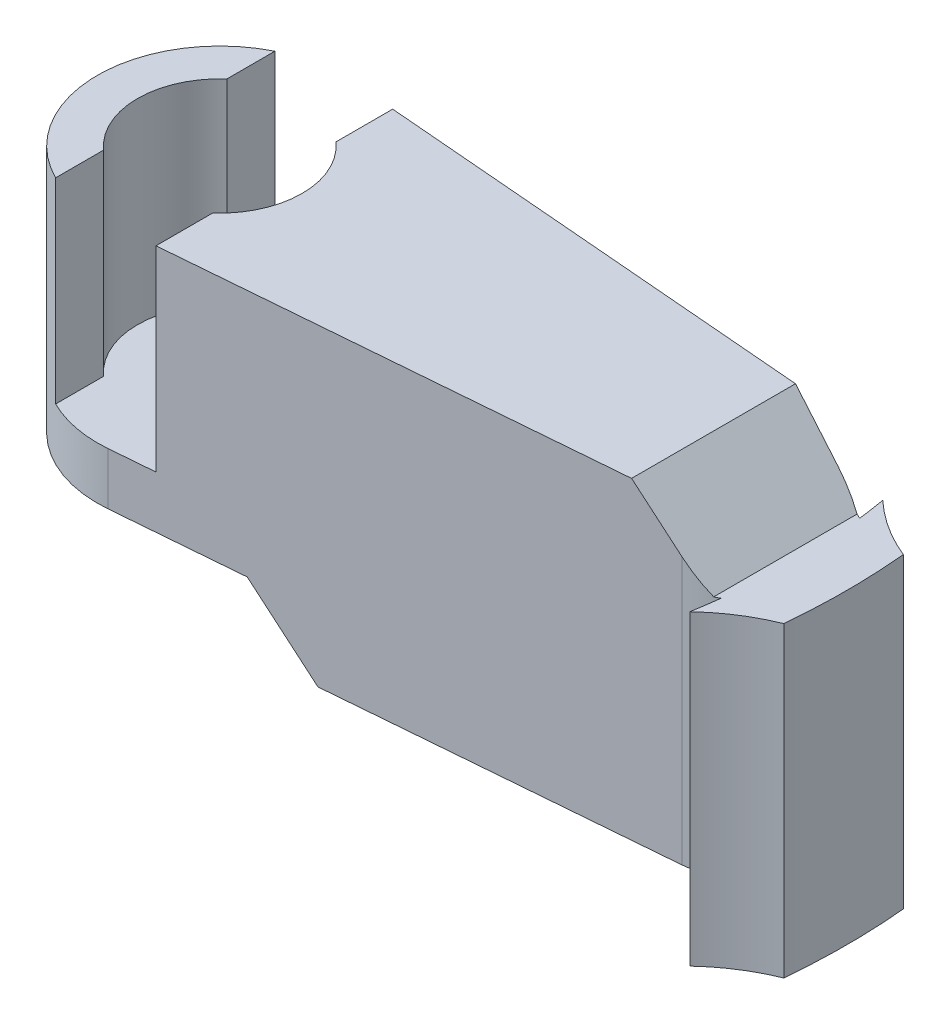
SolidWorks part; units mm, degrees
ref_plane "Front Plane" through (0, 0, 0) normal (0, 0, 1) x (1, 0, 0)
ref_plane "Top Plane" through (0, 0, 0) normal (0, 1, 0) x (1, 0, 0)
ref_plane "Right Plane" through (0, 0, 0) normal (1, 0, 0) x (0, 0, -1)
sketch "Sketch1" plane through (0, 0, 0) normal (0, 1, 0) x (1, 0, 0)
  line L0 (0.3096, -3.7372) -> (16.5482, -2.3918)
  line L1 (0.3096, 3.7372) -> (16.5482, 2.3918)
  line L2 (0, 0) -> (16.35, 0) construction
  arc A0 (0.3096, 3.7372) -> (0.3096, -3.7372) centre (0, 0) ccw
  arc A1 (16.5482, -2.3918) -> (16.5482, 2.3918) centre (16.35, 0) ccw
  arc A2 (3.75, 0) -> (0.3096, 3.7372) centre (0, 0) ccw construction
  arc A3 (0.3096, -3.7372) -> (3.75, 0) centre (0, 0) ccw construction
  dimension "D1" = 7.5
  dimension "D2" = 2.4
  dimension "D3" = 16.35
extrude "Boss-Extrude1" add sketch "Sketch1" along normal blind 9.6
sketch "Sketch2" plane through (0, 9.6, 0) normal (0, 1, 0) x (1, 0, 0)
  line L0 (-1.5, -1.809) -> (-1.5, -5.35) construction
  line L1 (-1.5, -5.35) -> (1.5, -5.35) construction
  line L2 (1.5, -5.35) -> (1.5, -1.809) construction
  line L3 (0, 0) -> (0, -2.35) construction
  line L4 (0, -2.35) -> (0, -5.35) construction
  line L5 (2.35, 0) -> (-2.35, 0) construction
  line L6 (-1.5, 1.809) -> (-1.5, 5.35) construction
  line L7 (-1.5, 5.35) -> (1.5, 5.35) construction
  line L8 (1.5, 5.35) -> (1.5, 1.809) construction
  line L9 (-1.67, -1.8872) -> (-1.67, -5.52)
  line L10 (-1.67, -5.52) -> (1.67, -5.52)
  line L11 (1.67, -5.52) -> (1.67, -1.8872)
  line L12 (1.67, 5.52) -> (1.67, 1.8872)
  line L13 (-1.67, 5.52) -> (1.67, 5.52)
  line L14 (-1.67, 1.8872) -> (-1.67, 5.52)
  arc A0 (1.5, -1.809) -> (1.5, 1.809) centre (0, 0) ccw construction
  arc A1 (-1.5, -1.809) -> (0, -2.35) centre (0, 0) ccw construction
  arc A2 (0, -2.35) -> (1.5, -1.809) centre (0, 0) ccw construction
  arc A3 (-1.5, 1.809) -> (-1.5, -1.809) centre (0, 0) ccw construction
  arc A4 (1.5, 1.809) -> (-1.5, 1.809) centre (0, 0) ccw construction
  arc A5 (1.67, -1.8872) -> (1.67, 1.8872) centre (0, 0) ccw
  arc A6 (-1.67, 1.8872) -> (-1.67, -1.8872) centre (0, 0) ccw
  point P12 (0, 0)
  dimension "D1" = 4.7
  dimension "D2" = 3
  dimension "D3" = 3
  dimension "D4" = 0.17
extrude "Cut-Extrude1" cut sketch "Sketch2" against normal blind 6
sketch "Sketch3" plane through (0, 0, 0) normal (0, -1, 0) x (1, 0, 0)
  line L0 (4.25, 3.4107) -> (4.25, -3.4107)
  line L1 (0, 0) -> (16.35, 0) construction
  line L2 (0.3096, -3.7372) -> (16.5482, -2.3918)
  line L3 (16.5482, 2.3918) -> (0.3096, 3.7372)
  line L4 (0.3096, -3.7372) -> (16.5482, -2.3918)
  line L5 (16.5482, 2.3918) -> (0.3096, 3.7372)
  arc A2 (0.3096, 3.7372) -> (0.3096, -3.7372) centre (0, 0) ccw
  arc A3 (16.5482, -2.3918) -> (16.5482, 2.3918) centre (16.35, 0) ccw
  arc A4 (0.3096, 3.7372) -> (0.3096, -3.7372) centre (0, 0) ccw
  arc A5 (16.5482, -2.3918) -> (16.5482, 2.3918) centre (16.35, 0) ccw
  point P8 (-3.75, 0)
  arc M7 (0.3096, 3.7372) -> (0.3096, -3.7372) centre (0, 0) ccw
  line M8 (0.3096, -3.7372) -> (16.5482, -2.3918)
  line M10 (16.5482, 2.3918) -> (0.3096, 3.7372)
  dimension "D2" = 8
  dimension "D1" = 0
extrude "Cut-Extrude2" cut sketch "Sketch3" against normal blind 2 contours L0 M10 M7 M8 region at (0.5434, 0, 0)
chamfer "Chamfer1" distance 2 angle 45 1 edges at (4.25, 0, 0)
sketch "Sketch4" plane through (0, 9.6, 0) normal (0, 1, 0) x (1, 0, 0)
  line L0 (16.35, 0) -> (0, 0) construction
  line L1 (16.35, 0) -> (17.6, 0) construction
  line L2 (17.3496, -2.9547) -> (17.3496, 2.9547) construction
  line L3 (18.75, 0) -> (19.19, 0) construction
  arc A0 (16.5482, -2.3918) -> (16.5482, 2.3918) centre (16.35, 0) ccw construction
  arc A1 (16.5482, -2.3918) -> (16.5482, 2.3918) centre (16.35, 0) ccw
  arc A2 (19.1038, 1.8312) -> (19.1038, -1.8312) centre (-0.3, 0) cw
  arc A3 (17.3496, -2.9547) -> (19.1038, -1.8312) centre (21.2218, -7.0691) cw
  arc A4 (17.3496, 2.9547) -> (17.4713, 2.1219) centre (0.04, 0) cw
  arc A5 (17.3496, 2.9547) -> (19.1038, 1.8312) centre (21.2218, 7.0691) ccw
  arc A6 (17.4713, -2.1219) -> (17.3496, -2.9547) centre (0.04, 0) cw
  arc A7 (17.6, 0) -> (17.4713, -2.1219) centre (0.04, 0) cw construction
  arc A8 (17.4713, 2.1219) -> (17.6, 0) centre (0.04, 0) cw construction
  point P9 (17.6, 0)
  point P13 (17.4286, -2.6369)
  point P14 (19.19, 0)
  point P20 (0, 0)
  point P21 (0, 0)
  point P22 (0, 0)
  point P23 (17.2243, -3.4173)
  point P25 (0, 0)
  point P26 (19.103, -1.8397)
  dimension "D3" = 19.49
  dimension "D4" = 5.65
  dimension "D5" = 17.56
  dimension "D6" = 5.65
  dimension "D1" = 1.25
  dimension "D2" = 0.44
  dimension "D7" = 19.33
  dimension "D8" = 21.246
extrude "Boss-Extrude2" add sketch "Sketch4" along normal offset from surface 2.2 and the other way blind 2 from surface contours A1 A6 A3 A2 A5 A4 region at (18.8119, 9.6, 0) up to face at (7.138, 9.6, 0) starting at face at (11.9495, 0, 0)
sketch "Sketch5" plane through (0, 9.6, 0) normal (0, 1, 0) x (1, 0, 0)
  line L0 (17.4713, 2.1219) -> (17.4713, -2.1219)
  arc A0 (16.5482, -2.3918) -> (16.5482, 2.3918) centre (16.35, 0) ccw construction
  arc A1 (16.5482, -2.3918) -> (16.5482, 2.3918) centre (16.35, 0) ccw
  arc A2 (17.3496, -2.9547) -> (17.4713, -2.1219) centre (0.04, 0) ccw construction
  arc M5 (16.5482, -2.3918) -> (16.5482, 2.3918) centre (16.35, 0) ccw
extrude "Cut-Extrude3" cut sketch "Sketch5" against normal blind 2.2 contours L0 M5 region at (17.9966, 9.6, 0)
chamfer "Chamfer2" distance 2.35 angle 45 1 edges at (17.4713, 9.6, 0)
